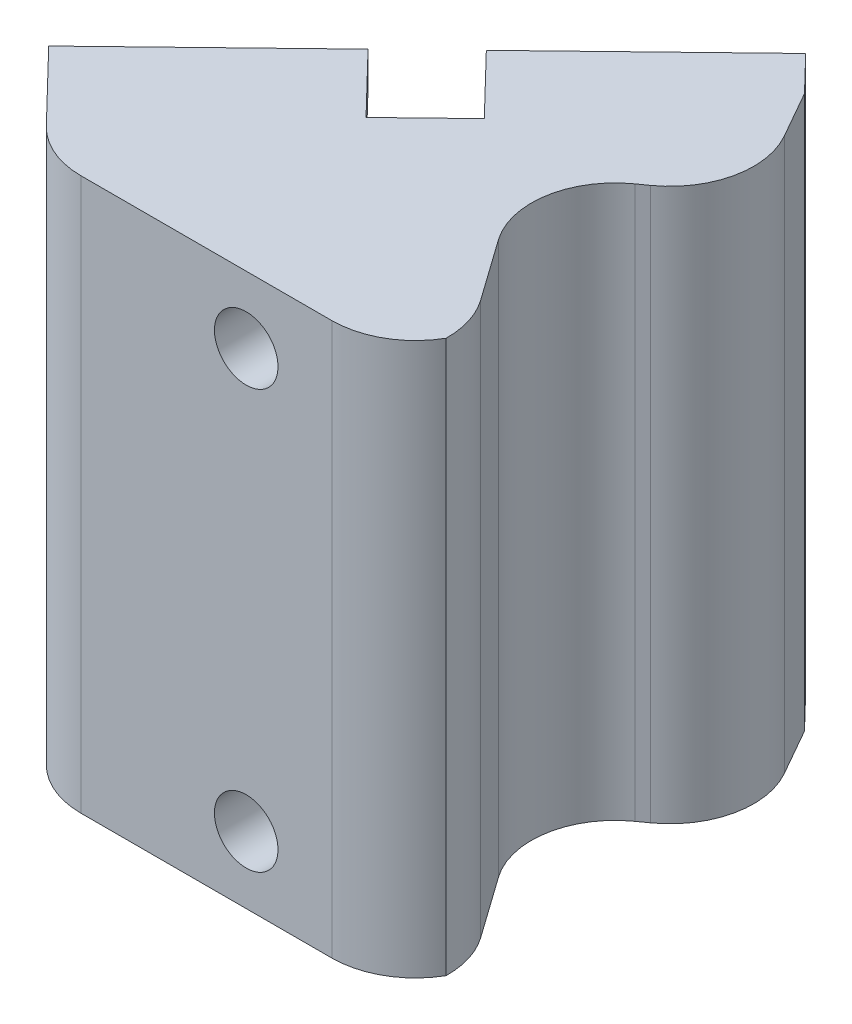
SolidWorks part; units mm, degrees
ref_plane "Front Plane" through (0, 0, 0) normal (0, 0, 1) x (1, 0, 0)
ref_plane "Top Plane" through (0, 0, 0) normal (0, 1, 0) x (1, 0, 0)
ref_plane "Right Plane" through (0, 0, 0) normal (1, 0, 0) x (0, 0, -1)
sketch "Sketch1" plane through (0, 0, 0) normal (0, 1, 0) x (1, 0, 0)
  line L0 (0, 0) -> (20, 0)
  line L1 (20, 0) -> (30.3817, 17.9816)
  line L2 (30.3817, 17.9816) -> (0, 0) construction
  line L3 (0, 0) -> (23.0113, 22.2369)
  line L4 (30.3817, 17.9816) -> (23.0113, 22.2369)
  dimension "D1" = 120
  dimension "D2" = 20
  dimension "D3" = 32
  dimension "D4" = 13.4
  dimension "D5" = 90
extrude "Boss-Extrude1" add sketch "Sketch1" along normal blind 33
sketch "Sketch2" plane through (0, 0, 0) normal (0.6949, 0, 0.7191) x (0.7191, 0, -0.6949)
  line L1 (0, 0) -> (32, 0)
  line L2 (0, 0) -> (0, 33)
  line L3 (0, 33) -> (32, 33)
  line L4 (32, 0) -> (32, 33)
extrude "Boss-Extrude2" add sketch "Sketch2" against normal blind 3
sketch "Sketch3" plane through (30, 0, 0) normal (0, 0, -1) x (-1, 0, 0)
  line L0 (18, -986.4883) -> (18, 49013.5117) construction
  line L1 (-972.5, 16.5) -> (49027.5, 16.5) construction
  line L3 (30, 33) -> (30, 0) construction
  line L4 (30, 33) -> (10, 33) construction
  circle A0 centre (18, 29) radius 1.9
  circle A1 centre (18, 4) radius 1.9
  dimension "D2" = 3.8
  dimension "D3" = 3.8
  dimension "D1" = 12
  dimension "D4" = 12.5
  dimension "D5" = 12.5
  dimension "D6" = 16.5
extrude "Cut-Extrude1" cut sketch "Sketch3" along normal blind 7
fillet "Fillet1" radius 5 1 edges at (20, 16.5, 0)
sketch "Sketch5" plane through (-2.0847, 0, -2.1573) normal (-0.6949, 0, -0.7191) x (-0.7191, 0, 0.6949)
  line L0 (-32, 16.5) -> (0, 16.5) construction
  line L3 (-16, 33) -> (-16, 0) construction
  line L8 (0, 33) -> (0, 0) construction
  line L9 (-32, 33) -> (0, 33) construction
  line L10 (0, 0) -> (-32, 0) construction
  line L11 (-32, 33) -> (-32, 0) construction
  circle A0 centre (-28.3, 28.4) radius 2
  circle A1 centre (-3.7, 28.4) radius 2
  circle A2 centre (-28.3, 4.6) radius 2
  circle A3 centre (-3.7, 4.6) radius 2
  dimension "D6" = 4
  dimension "D7" = 4
  dimension "D8" = 4
  dimension "D9" = 4
  dimension "D1" = 12.3
  dimension "D2" = 12.3
  dimension "D3" = 12.3
  dimension "D4" = 12.3
  dimension "D5" = 11.9
  dimension "D10" = 11.9
  dimension "D11" = 11.9
  dimension "D12" = 11.9
extrude "Boss-Extrude3" add sketch "Sketch5" along normal blind 5
sketch "Sketch6" plane through (-2.0847, 0, -2.1573) normal (-0.6949, 0, -0.7191) x (-0.7191, 0, 0.6949)
  line L0 (-2, 2) -> (-2, 31)
  line L1 (0, 0) -> (-32, 0)
  line L2 (0, 0) -> (0, 33)
  line L3 (0, 33) -> (-32, 33)
  line L4 (-32, 0) -> (-32, 33)
  line L5 (-2, 31) -> (-30, 31)
  line L6 (-30, 2) -> (-30, 31)
  line L7 (-2, 2) -> (-30, 2)
  dimension "D1" = 2
extrude "Boss-Extrude4" add sketch "Sketch6" along normal blind 5
sketch "Sketch9" plane through (-2.0847, 0, -2.1573) normal (-0.6949, 0, -0.7191) x (-0.7191, 0, 0.6949)
  line L0 (-28.3, 26.4) -> (-30, 26.4)
  line L3 (-30, 27.3464) -> (-30, 5.6536) construction
  line L5 (-30, 26.4) -> (-30, 31)
  line L7 (-30, 31) -> (-26.3, 31)
  line L8 (-2, 31) -> (-30, 31) construction
  line L9 (-26.3, 31) -> (-26.3, 28.4)
  line L10 (-26.3, 28.4) -> (-28.3, 26.4)
  line L11 (-5.7, 28.4) -> (-5.7, 31)
  line L13 (-5.7, 31) -> (-2, 31)
  line L14 (-2, 31) -> (-2, 26.4)
  line L15 (-2, 5.6536) -> (-2, 27.3464) construction
  line L17 (-2, 26.4) -> (-3.7, 26.4)
  line L18 (-3.7, 26.4) -> (-5.7, 28.4)
  line L20 (-3.7, 6.6) -> (-2, 6.6)
  line L21 (-2, 5.6536) -> (-2, 27.3464) construction
  line L22 (-2, 6.6) -> (-2, 2)
  line L24 (-2, 2) -> (-5.7, 2)
  line L25 (-30, 2) -> (-2, 2) construction
  line L27 (-5.7, 2) -> (-5.7, 4.6)
  line L28 (-5.7, 4.6) -> (-3.7, 6.6)
  line L29 (-28.3, 6.6) -> (-30, 6.6)
  line L30 (-30, 6.6) -> (-30, 2)
  line L31 (-30, 2) -> (-26.3, 2)
  line L32 (-26.3, 2) -> (-26.3, 4.6)
  line L33 (-26.3, 4.6) -> (-28.3, 6.6)
  arc A9 (-30, 27.3464) -> (-30, 29.4536) centre (-28.3, 28.4) ccw construction
  arc A10 (-30, 27.3464) -> (-30, 29.4536) centre (-28.3, 28.4) ccw construction
  arc A11 (-2, 29.4536) -> (-2, 27.3464) centre (-3.7, 28.4) ccw construction
  arc A12 (-2, 29.4536) -> (-2, 27.3464) centre (-3.7, 28.4) ccw construction
  arc A13 (-2, 5.6536) -> (-2, 3.5464) centre (-3.7, 4.6) ccw construction
  arc A14 (-2, 5.6536) -> (-2, 3.5464) centre (-3.7, 4.6) ccw construction
  arc A15 (-30, 3.5464) -> (-30, 5.6536) centre (-28.3, 4.6) ccw construction
  arc A16 (-30, 3.5464) -> (-30, 5.6536) centre (-28.3, 4.6) ccw construction
extrude "Boss-Extrude5" add sketch "Sketch9" along normal blind 5
sketch "Sketch7" plane through (-5.5592, 0, -5.7528) normal (-0.6949, 0, -0.7191) x (-0.7191, 0, 0.6949)
  line L2 (-5.7, 31) -> (-26.3, 31) construction
  line L3 (-18.5, 90.844) -> (-13.5, 90.844)
  line L4 (-18.5, 90.844) -> (-18.5, -28.844)
  line L5 (-18.5, -28.844) -> (-13.5, -28.844)
  line L6 (-13.5, 90.844) -> (-13.5, -28.844)
  line L8 (-18.5, 90.844) -> (-13.5, -28.844) construction
  line L9 (-18.5, -28.844) -> (-13.5, 90.844) construction
  circle A0 centre (-28.3, 28.4) radius 0.75
  circle A1 centre (-3.7, 28.4) radius 0.75
  circle A2 centre (-3.7, 4.6) radius 0.75
  circle A3 centre (-28.3, 4.6) radius 0.75
  point P0 (-16, 31)
  dimension "D3" = 1.5
  dimension "D4" = 1.5
  dimension "D5" = 1.5
  dimension "D6" = 1.5
  dimension "D1" = 5
extrude "Cut-Extrude3" cut sketch "Sketch7" against normal blind 5
sketch "Sketch8" plane through (0, 33, 0) normal (0, 1, 0) x (1, 0, 0)
  line L0 (17.7453, 28.95) -> (16.8781, 39.6256)
  line L1 (16.8781, 39.6256) -> (45.2125, 18.1015)
  line L2 (45.2125, 18.1015) -> (33.0366, 2.0731)
  line L3 (17.7453, 28.95) -> (33.0366, 2.0731)
extrude "Cut-Extrude4" cut sketch "Sketch8" against normal through all
sketch "Sketch10" plane through (0, 33, 0) normal (0, 1, 0) x (1, 0, 0)
  line L0 (23.3269, 19.1394) -> (15.018, 13.2412)
  line L1 (19.4937, 25.8771) -> (27.1602, 12.4018) construction
  line L2 (15.018, 13.2412) -> (21.9814, 3.4319)
  line L3 (21.4434, 2.5) -> (27.1602, 12.4018) construction
  line L4 (21.9814, 3.4319) -> (33.5929, 11.6746)
  line L5 (33.5929, 11.6746) -> (23.3269, 19.1394)
extrude "Cut-Extrude5" cut sketch "Sketch10" against normal through all
fillet "Fillet4" radius 5 4 edges at (21.9814, 16.5, -3.4319) (15.018, 16.5, -13.2412) (23.3269, 16.5, -19.1394) (0, 16.5, 0)
equation "\"D2@Sketch5\"=\"D1@Sketch5\""
equation "\"D3@Sketch5\"=\"D1@Sketch5\""
equation "\"D4@Sketch5\"=\"D1@Sketch5\""
equation "\"D7@Sketch5\"=\"D6@Sketch5\""
equation "\"D9@Sketch5\"=\"D6@Sketch5\""
equation "\"D8@Sketch5\"=\"D6@Sketch5\""
equation "\"D10@Sketch5\"=\"D5@Sketch5\""
equation "\"D11@Sketch5\"=\"D5@Sketch5\""
equation "\"D12@Sketch5\"=\"D5@Sketch5\""
